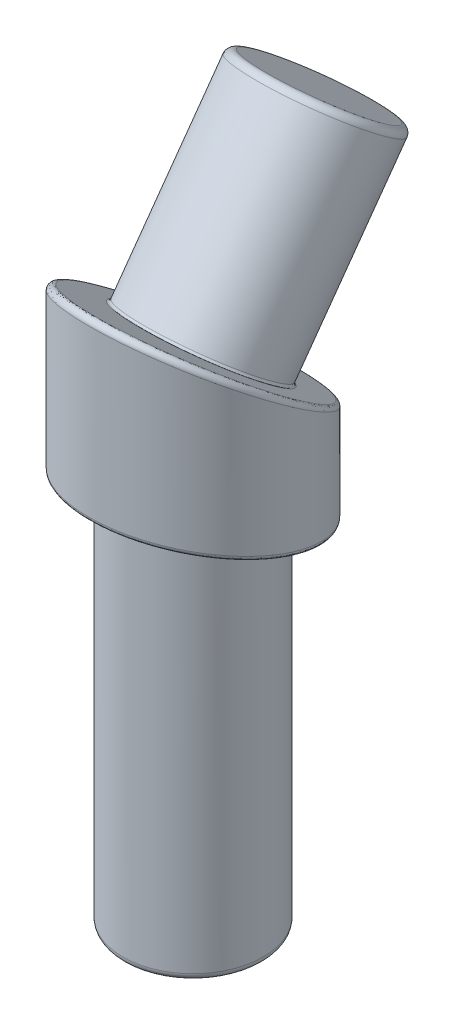
SolidWorks part; units mm, degrees
material "PE High Density"
ref_plane "Front Plane" through (0, 0, 0) normal (0, 0, 1) x (1, 0, 0)
ref_plane "Top Plane" through (0, 0, 0) normal (0, 1, 0) x (1, 0, 0)
ref_plane "Right Plane" through (0, 0, 0) normal (1, 0, 0) x (0, 0, -1)
sketch "Sketch1" plane through (0, 0, 0) normal (0, 1, 0) x (1, 0, 0)
  circle A0 centre (0, 0) radius 2.925
  dimension "D1" = 5.85
extrude "Boss-Extrude1" add sketch "Sketch1" along normal blind 16.35
sketch "Sketch2" plane through (0, 0, 0) normal (1, 0, 0) x (0, 0, -1)
  line L0 (0, 0) -> (0, 15.475) construction
  line L1 (-4.35, 16.7763) -> (-4.35, 24.2263)
  line L2 (-4.35, 24.2263) -> (4.35, 17.9737)
  line L3 (4.35, 17.9737) -> (4.35, 14.1737)
  line L4 (4.35, 14.1737) -> (-4.35, 16.7763)
  line L5 (2.925, 0) -> (2.925, 16.35) construction
  line L6 (-2.925, 0) -> (2.925, 0) construction
  line L7 (0, 15.475) -> (0, 21.1)
  point P3 (2.925, 14.6)
  dimension "D1" = 8.7
  dimension "D2" = 14.6
  dimension "D3" = 3.8
  dimension "D4" = 7.45
ref_plane "Plane2" through (0, 14.2039, -4.249) normal (0, 0.9581, -0.2866) x (0, 0.2866, 0.9581)
sketch "Sketch4" plane through (0, 14.2039, -4.249) normal (0, 0.9581, -0.2866) x (0, 0.2866, 0.9581)
  ellipse E0 centre (4.4351, 0) end of major axis (-0.1054, 0) minor radius 4.325
  dimension "D1" = 8.65
ref_plane "Plane3" through (0, 13.9135, -9.9995) normal (0, -0.812, 0.5836) x (0, -0.5836, -0.812)
sketch "Sketch5" plane through (0, 13.9135, -9.9995) normal (0, -0.812, 0.5836) x (0, -0.5836, -0.812)
  ellipse E0 centre (-12.314, 0) end of major axis (-6.9571, 0) minor radius 4.325
loft "Loft1" add profiles "Sketch5", "Sketch4" connector at (0.0163, 17.9737, -4.35) connector at (-0.1413, 14.1744, -4.3477)
sketch "Sketch6" plane through (0, 13.9135, -9.9995) normal (0, 0.812, -0.5836) x (1, 0, 0)
  line L0 (0, -17.6709) -> (0, -14.8709) construction
  circle A0 centre (0, -11.8859) radius 2.985
  ellipse E0 centre (0, -12.314) end of major axis (0, -17.6709) minor radius 4.325 construction
  dimension "D1" = 5.97
  dimension "D2" = 2.8
extrude "Boss-Extrude2" add sketch "Sketch6" along normal blind 8.43
fillet "Fillet1" radius 0.3 2 edges at (0, 0, 2.925) (0, 29.4377, -2.8435)
fillet "Fillet2" radius 0.2 2 edges at (0, 14.1737, -4.35) (0, 24.2263, 4.35)
fillet "Fillet3" radius 0.1 2 edges at (0, 19.1081, -2.7716) (0, 14.6, -2.925)
